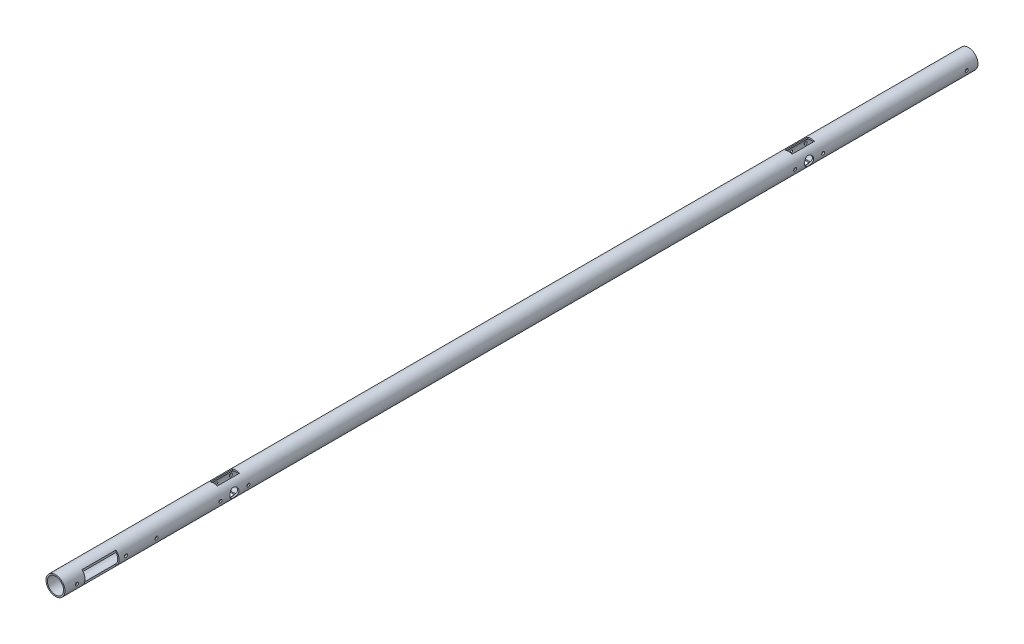
SolidWorks part; units mm, degrees
ref_plane "Front" through (0, 0, 0) normal (0, 0, 1) x (1, 0, 0)
ref_plane "Top" through (0, 0, 0) normal (0, 1, 0) x (1, 0, 0)
ref_plane "Right" through (0, 0, 0) normal (1, 0, 0) x (0, 0, -1)
sketch "Sketch1" plane through (0, 0, 0) normal (0, 0, 1) x (1, 0, 0)
  circle A0 centre (0, 0) radius 9.36
  circle A1 centre (0, 0) radius 7.99
extrude "Extrude1" add sketch "Sketch1" along normal blind 900
sketch "Sketch4" plane through (0, 0, 0) normal (0, 1, 0) x (1, 0, 0)
  line L1 (-3.5, -155.425) -> (3.5, -155.425)
  line L2 (-3.5, -155.425) -> (-3.5, -177.425)
  line L3 (-3.5, -177.425) -> (3.5, -177.425)
  line L4 (3.5, -155.425) -> (3.5, -177.425)
  line L5 (-3.5, -722) -> (3.5, -722)
  line L6 (-3.5, -722) -> (-3.5, -744)
  line L7 (-3.5, -744) -> (3.5, -744)
  line L8 (3.5, -722) -> (3.5, -744)
extrude "Cut-Extrude3" cut sketch "Sketch4" along normal through all
sketch "Sketch5" plane through (0, 0, 0) normal (0, 1, 0) x (1, 0, 0)
  line L0 (-3.5, -155.425) -> (-3.5, -177.425) construction
  line L1 (-3.5, -158.425) -> (3.5, -158.425)
  line L2 (-3.5, -158.425) -> (-3.5, -174.425)
  line L3 (-3.5, -174.425) -> (3.5, -174.425)
  line L4 (3.5, -158.425) -> (3.5, -174.425)
  line L5 (3.5, -177.425) -> (3.5, -155.425) construction
  line L6 (3.5, -744) -> (3.5, -722) construction
  line L7 (-3.5, -725) -> (3.5, -725)
  line L8 (-3.5, -725) -> (-3.5, -741)
  line L9 (-3.5, -741) -> (3.5, -741)
  line L10 (3.5, -725) -> (3.5, -741)
extrude "Cut-Extrude4" cut sketch "Sketch5" against normal through all
sketch "Sketch6" plane through (0, 0, 0) normal (1, 0, 0) x (0, 0, -1)
  line L0 (-741, 0) -> (-725, 0) construction
  line L1 (-741, 0) -> (-725, 0) construction
  line L2 (-741, 0) -> (-725, 0) construction
  circle A0 centre (-166.425, 0) radius 1
  circle A1 centre (-733, 0) radius 1
  circle A2 centre (-282.57, 0) radius 1.5
extrude "Cut-Extrude5" cut sketch "Sketch6" against normal through all
sketch "Sketch7" plane through (0, 0, 0) normal (1, 0, 0) x (0, 0, -1)
  line L0 (-741, 0) -> (-725, 0) construction
  line L1 (-741, 0) -> (-725, 0) construction
  circle A0 centre (-166.425, 0) radius 4.5
  circle A1 centre (-733, 0) radius 4.5
extrude "Cut-Extrude6" cut sketch "Sketch7" along normal through all
sketch "Sketch8" plane through (0, 0, 0) normal (1, 0, 0) x (0, 0, -1)
  line L0 (-741, 0) -> (-725, 0) construction
  line L1 (-741, 0) -> (-725, 0) construction
  circle A0 centre (-152.6138, 0) radius 1.5
  circle A1 centre (-180.1763, 0) radius 1.5
  circle A2 centre (-746.7513, 0) radius 1.5
  circle A3 centre (-719.1888, 0) radius 1.5
  circle A4 centre (-809.725, 0) radius 1.55
  circle A5 centre (-839.885, 0) radius 1.55
  circle A6 centre (-888.255, 0) radius 1.55
  circle A7 centre (-11.1125, 0) radius 1.5
extrude "Cut-Extrude7" cut sketch "Sketch8" against normal through all and the other way through all
sketch "Sketch9" plane through (0, 0, 0) normal (0, 1, 0) x (1, 0, 0)
  line L1 (6.36, -846.675) -> (12.5, -846.675)
  line L2 (6.36, -846.675) -> (6.36, -880.175)
  line L3 (6.36, -880.175) -> (12.5, -880.175)
  line L4 (12.5, -846.675) -> (12.5, -880.175)
extrude "Cut-Extrude8" cut sketch "Sketch9" against normal through all and the other way through all
